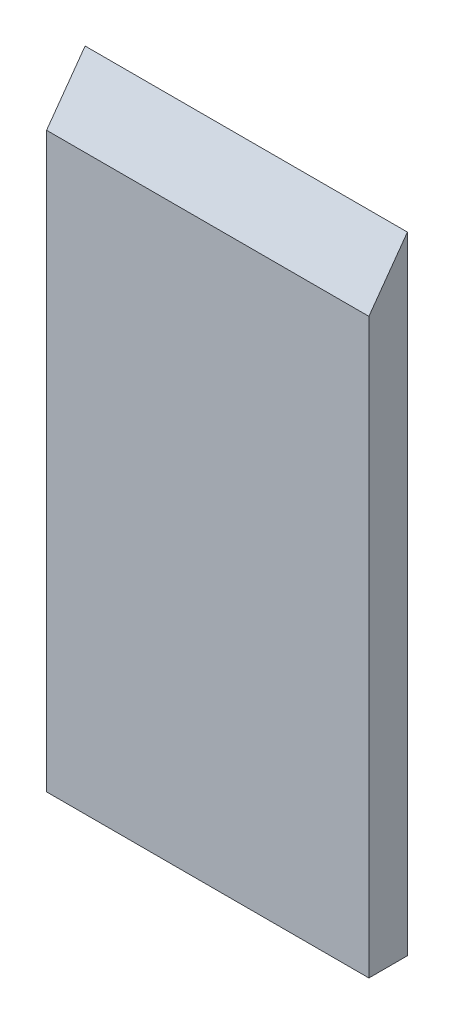
SolidWorks part; units mm, degrees
ref_plane "Alzado" through (0, 0, 0) normal (0, 0, 1) x (1, 0, 0)
ref_plane "Planta" through (0, 0, 0) normal (0, 1, 0) x (1, 0, 0)
ref_plane "Vista lateral" through (0, 0, 0) normal (1, 0, 0) x (0, 0, -1)
sketch "Croquis1" plane through (0, 0, 0) normal (0, 1, 0) x (1, 0, 0)
  line L1 (-169.9219, 44.6777) -> (190.0781, 44.6777)
  line L2 (-169.9219, 44.6777) -> (-169.9219, 1.6677)
  line L3 (-169.9219, 1.6677) -> (190.0781, 1.6677)
  line L4 (190.0781, 44.6777) -> (190.0781, 1.6677)
  dimension "D1" = 360
  dimension "D2" = 43.01
extrude "Saliente-Extruir1" add sketch "Croquis1" along normal blind 700
sketch "Croquis5" plane through (190.0781, 0, 0) normal (1, 0, 0) x (0, 0, -1)
  line L0 (44.6777, 700) -> (1.6677, 640)
  line L1 (1.6677, 700) -> (1.6677, 0) construction
  line L2 (1.6677, 640) -> (1.6677, 700)
  line L3 (1.6677, 700) -> (44.6777, 700)
  dimension "D1" = 60
extrude "Cortar-Extruir4" cut sketch "Croquis5" against normal blind 360
